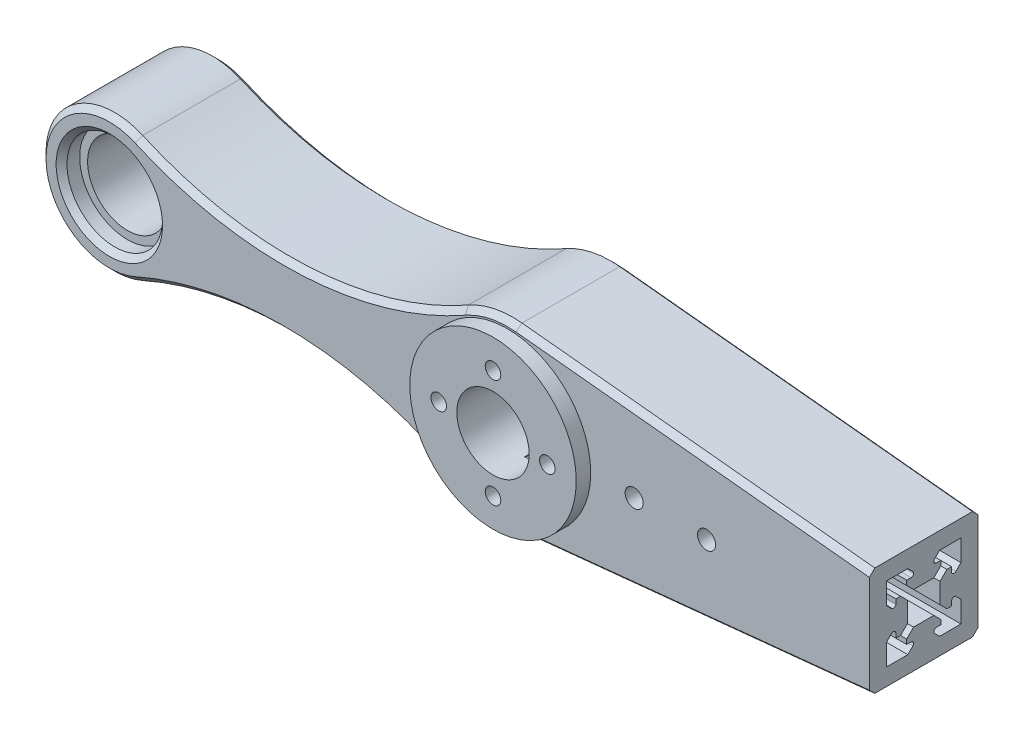
SolidWorks part; units mm, degrees
ref_plane "Front Plane" through (0, 0, 0) normal (0, 0, 1) x (1, 0, 0)
ref_plane "Top Plane" through (0, 0, 0) normal (0, 1, 0) x (1, 0, 0)
ref_plane "Right Plane" through (0, 0, 0) normal (1, 0, 0) x (0, 0, -1)
sketch "Sketch1" plane through (0, 0, 0) normal (0, 0, 1) x (1, 0, 0)
  line L0 (100, 15) -> (100, -15)
  line L1 (2.5191, 24.8728) -> (100, 15)
  line L2 (100, -15) -> (2.5191, -24.8728)
  line L3 (0, 0) -> (-110, 0) construction
  line L4 (0, 0) -> (0, 15) construction
  circle A0 centre (0, 0) radius 10
  circle A2 centre (55, 0) radius 2.5
  circle A4 centre (35, 0) radius 2.5
  circle A5 centre (0, 15) radius 2.15
  circle A6 centre (15, 0) radius 2.15
  circle A7 centre (0, -15) radius 2.15
  circle A8 centre (-15, 0) radius 2.15
  circle A9 centre (0, 0) radius 25
  circle A10 centre (-110, 0) radius 13.2
  arc A11 (-102.281, 17.3614) -> (-102.281, -17.3614) centre (-110, 0) ccw
  arc A12 (-102.281, 17.3614) -> (-12.3309, 21.7474) centre (-61.6545, 108.7369) ccw
  arc A13 (-102.281, -17.3614) -> (-12.3309, -21.7474) centre (-61.6545, -108.7369) cw
  point P6 (100, 0)
  point P25 (0, 0)
  dimension "D1" = 20
  dimension "D2" = 50
  dimension "D8" = 5
  dimension "D11" = 4.3
  dimension "D13" = 26.4
  dimension "D14" = 38
  dimension "D17" = 100
  dimension "D18" = 100
  dimension "D3" = 30
  dimension "D4" = 100
  dimension "D5" = 35
  dimension "D6" = 20
  dimension "D10" = 15
  dimension "D15" = 90
  dimension "D16" = 110
  dimension "D12" = 4
extrude "Boss-Extrude1" add sketch "Sketch1" along normal blind 30
sketch "Sketch3" plane through (100, 0, 0) normal (1, 0, 0) x (0, 0, -1)
  line L0 (-12.1971, 4.5) -> (-17.8029, 4.5)
  line L1 (-17.8029, 4.5) -> (-19.7101, 6.4071)
  line L2 (-19.7101, 6.4071) -> (-19.7101, 7.7)
  line L3 (-19.7101, 7.7) -> (-18.4828, 7.7)
  line L4 (-17.9879, 8.895) -> (-19.3879, 10.295)
  line L5 (-25.295, 4.3879) -> (-23.895, 2.9879)
  line L6 (-22.7, 3.4828) -> (-22.7, 4.7101)
  line L7 (-22.7, 4.7101) -> (-21.4071, 4.7101)
  line L8 (-21.4071, 4.7101) -> (-19.5, 2.8029)
  line L9 (-19.5, 2.8029) -> (-19.5, -2.8029)
  line L10 (-19.5, -2.8029) -> (-21.4071, -4.7101)
  line L11 (-21.4071, -4.7101) -> (-22.7, -4.7101)
  line L12 (-22.7, -4.7101) -> (-22.7, -3.4828)
  line L13 (-23.895, -2.9879) -> (-25.295, -4.3879)
  line L14 (-19.3879, -10.295) -> (-17.9879, -8.895)
  line L15 (-18.4828, -7.7) -> (-19.7101, -7.7)
  line L16 (-19.7101, -7.7) -> (-19.7101, -6.4071)
  line L17 (-19.7101, -6.4071) -> (-17.8029, -4.5)
  line L18 (-17.8029, -4.5) -> (-12.1971, -4.5)
  line L19 (-19.3879, -10.295) -> (-25.295, -10.295)
  line L20 (-25.295, -10.295) -> (-25.295, -4.3879)
  line L21 (-25.295, 4.3879) -> (-25.295, 10.295)
  line L22 (-25.295, 10.295) -> (-19.3879, 10.295)
  line L23 (-15, 15.274) -> (-15, -14.726) construction
  line L24 (-4.705, 10.295) -> (-10.6121, 10.295)
  line L25 (-4.705, 4.3879) -> (-4.705, 10.295)
  line L26 (-4.705, -10.295) -> (-4.705, -4.3879)
  line L27 (-10.6121, -10.295) -> (-4.705, -10.295)
  line L28 (-10.2899, -6.4071) -> (-12.1971, -4.5)
  line L29 (-10.2899, -7.7) -> (-10.2899, -6.4071)
  line L30 (-11.5172, -7.7) -> (-10.2899, -7.7)
  line L31 (-10.6121, -10.295) -> (-12.0121, -8.895)
  line L32 (-6.105, -2.9879) -> (-4.705, -4.3879)
  line L33 (-7.3, -4.7101) -> (-7.3, -3.4828)
  line L34 (-8.5929, -4.7101) -> (-7.3, -4.7101)
  line L35 (-10.5, -2.8029) -> (-8.5929, -4.7101)
  line L36 (-10.5, 2.8029) -> (-10.5, -2.8029)
  line L37 (-8.5929, 4.7101) -> (-10.5, 2.8029)
  line L38 (-7.3, 4.7101) -> (-8.5929, 4.7101)
  line L39 (-7.3, 3.4828) -> (-7.3, 4.7101)
  line L40 (-4.705, 4.3879) -> (-6.105, 2.9879)
  line L41 (-12.0121, 8.895) -> (-10.6121, 10.295)
  line L42 (-10.2899, 7.7) -> (-11.5172, 7.7)
  line L43 (-10.2899, 6.4071) -> (-10.2899, 7.7)
  line L44 (-12.1971, 4.5) -> (-10.2899, 6.4071)
  line L45 (-30, 15) -> (0, 15) construction
  arc A0 (-12.0121, -8.895) -> (-11.5172, -7.7) centre (-11.5172, -8.4) cw
  arc A1 (-18.4828, 7.7) -> (-17.9879, 8.895) centre (-18.4828, 8.4) ccw
  arc A2 (-7.3, -3.4828) -> (-6.105, -2.9879) centre (-6.6, -3.4828) cw
  arc A3 (-6.105, 2.9879) -> (-7.3, 3.4828) centre (-6.6, 3.4828) cw
  arc A4 (-23.895, 2.9879) -> (-22.7, 3.4828) centre (-23.4, 3.4828) ccw
  arc A5 (-22.7, -3.4828) -> (-23.895, -2.9879) centre (-23.4, -3.4828) ccw
  arc A6 (-11.5172, 7.7) -> (-12.0121, 8.895) centre (-11.5172, 8.4) cw
  arc A7 (-17.9879, -8.895) -> (-18.4828, -7.7) centre (-18.4828, -8.4) ccw
  point P0 (-15, 4.5)
  point P64 (-10.5, 0)
  point P68 (-15, 15)
  dimension "D7" = 0.7
  dimension "D16" = 0.7
  dimension "D31" = 0.7
  dimension "D1" = 5.6059
  dimension "D2" = 2.6971
  dimension "D3" = 1.2929
  dimension "D4" = 2.595
  dimension "D5" = 135
  dimension "D6" = 1.2934
  dimension "D8" = 1.9799
  dimension "D9" = 135
  dimension "D10" = 1.2272
  dimension "D11" = 5.6059
  dimension "D12" = 2.6971
  dimension "D13" = 1.2929
  dimension "D14" = 1.2272
  dimension "D15" = 1.2934
  dimension "D17" = 1.9799
  dimension "D18" = 225
  dimension "D19" = 5.9071
  dimension "D20" = 135
  dimension "D21" = 90
  dimension "D22" = 135
  dimension "D23" = 2.595
  dimension "D24" = 135
  dimension "D25" = 135
  dimension "D26" = 1.2934
  dimension "D27" = 5.9071
  dimension "D28" = 1.9799
  dimension "D29" = 135
  dimension "D30" = 1.2934
  dimension "D32" = 1.2272
  dimension "D33" = 90
  dimension "D34" = 135
  dimension "D35" = 1.2929
  dimension "D36" = 2.595
  dimension "D37" = 2.6971
  dimension "D38" = 5.6059
  dimension "D39" = 5.9071
extrude "Cut-Extrude1" cut sketch "Sketch3" against normal blind 100 contours L0 L1 L2 L3 A1 L4 L22 L21 L5 A4 L6 L7 L8 L9 L10 L11 L12 A5 L13 L20 L19 L14 A7 L15 L16 L17 L18 L28 L29 L30 A0 L31 L27 L26 L32 A2 L33 L34 L35 L36 L37 L38 L39 A3 L40 L25 L24 L41 A6 L42 L43 L44
sketch "Sketch5" plane through (0, 0, 30) normal (0, 0, 1) x (1, 0, 0)
  circle A0 centre (0, 0) radius 23
  circle A11 centre (0, -15) radius 2.15 construction
  circle A12 centre (15, 0) radius 2.15 construction
  circle A13 centre (0, 15) radius 2.15 construction
  circle A14 centre (-15, 0) radius 2.15 construction
  circle A15 centre (0, 0) radius 10 construction
  circle A16 centre (0, -15) radius 2.15
  circle A17 centre (15, 0) radius 2.15
  circle A18 centre (0, 15) radius 2.15
  circle A19 centre (-15, 0) radius 2.15
  circle A20 centre (0, 0) radius 10
  dimension "D1" = 46
extrude "Boss-Extrude2" add sketch "Sketch5" along normal blind 4
sketch "Sketch6" plane through (0, 0, 0) normal (0, 0, -1) x (-1, 0, 0)
  circle A0 centre (0, 15) radius 4
  circle A1 centre (15, 0) radius 4
  circle A2 centre (0, -15) radius 4
  circle A3 centre (-15, 0) radius 4
  dimension "D1" = 8
extrude "Cut-Extrude2" cut sketch "Sketch6" against normal blind 20
chamfer "Chamfer1" distance 1.5 angle 45 17 edges at (51.2595, 19.9364, 0) (51.2595, 19.9364, 30) (-5.1488, 24.4641, 0) (-5.1488, 24.4641, 30) (-56.7843, 8.8556, 0) (-56.7843, 8.8556, 30) (51.2595, -19.9364, 0) (51.2595, -19.9364, 30) (-129, 0, 0) (-129, 0, 30) (-5.1488, -24.4641, 0) (-5.1488, -24.4641, 30) (-56.7843, -8.8556, 0) (-56.7843, -8.8556, 30) (10, 0, 0) (-96.8, 0, 30) (-96.8, 0, 0)
sketch "Sketch7" plane through (0, 0, 30) normal (0, 0, 1) x (1, 0, 0)
  circle A0 centre (-110, 0) radius 11
  circle A1 centre (-110, 0) radius 13.2 construction
  circle A2 centre (-110, 0) radius 13.2
  dimension "D1" = 22
extrude "Boss-Extrude3" add sketch "Sketch7" against normal blind 20 from offset 5
